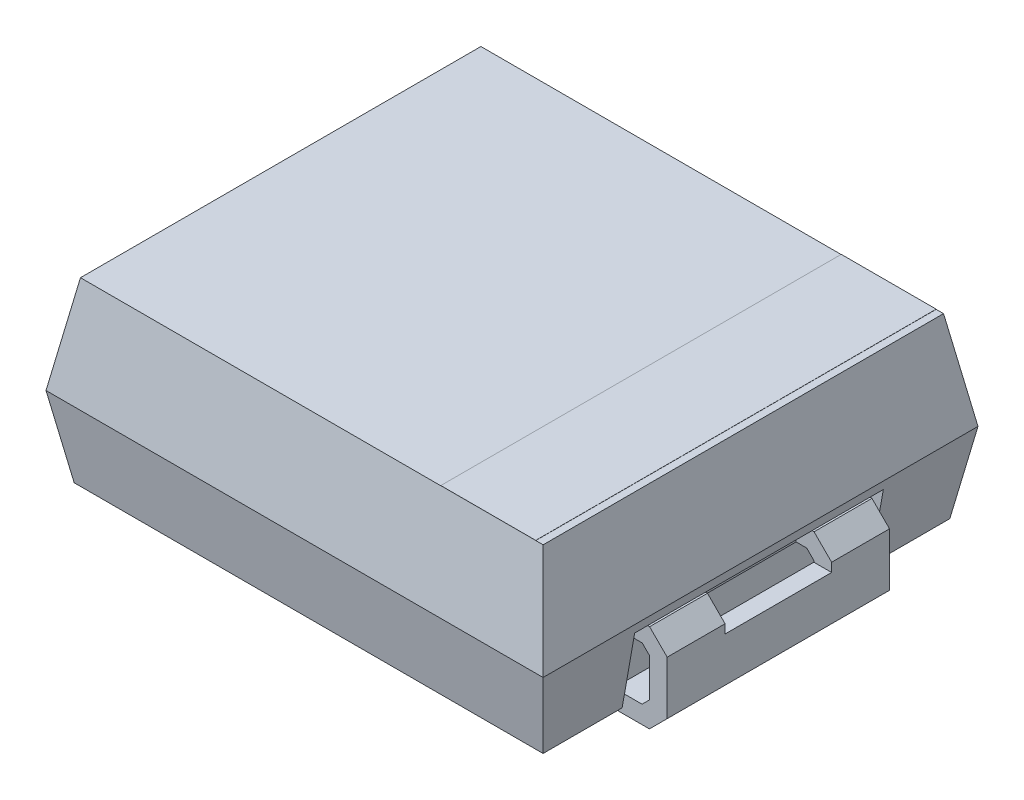
SolidWorks part; units mm, degrees
ref_plane "Front Plane" through (0, 0, 0) normal (0, 0, 1) x (1, 0, 0)
ref_plane "Top Plane" through (0, 0, 0) normal (0, 1, 0) x (1, 0, 0)
ref_plane "Right Plane" through (0, 0, 0) normal (1, 0, 0) x (0, 0, -1)
sketch "Sketch2" plane through (0, 0, 0) normal (1, 0, 0) x (0, 0, -1)
  line L1 (3.11, 2.794) -> (-3.11, 2.794)
  line L2 (3.11, 2.794) -> (3.11, 0)
  line L3 (3.11, 0) -> (-3.11, 0)
  line L4 (-3.11, 2.794) -> (-3.11, 0)
  dimension "D1" = 2.794
  dimension "D2" = 6.22
extrude "Base-Extrude" add sketch "Sketch2" along normal blind 7.1095
chamfer "Chamfer1" distance 1.397 angle 10 4 edges at (7.1095, 0, 0) (0, 0, 0) (3.5547, 0, -3.11) (3.5547, 0, 3.11)
sketch "Sketch3" plane through (0, 0, 0) normal (-1, 0, 0) x (0, 0, 1)
  line L0 (2.8636, 0) -> (-2.8636, 0) construction
  line L1 (-1.778, 1.27) -> (1.778, 1.27)
  line L2 (-1.778, 1.27) -> (-1.778, 0)
  line L3 (-1.778, 0) -> (1.778, 0)
  line L4 (1.778, 1.27) -> (1.778, 0)
  dimension "D1" = 1.27
  dimension "D2" = 1.778
  dimension "D3" = 3.556
extrude "Cut-Extrude1" cut sketch "Sketch3" against normal blind 0.508
sketch "Sketch4" plane through (7.1095, 0, 0) normal (1, 0, 0) x (0, 0, -1)
  line L0 (-1.778, 0) -> (1.778, 0)
  line L1 (2.8636, 0) -> (-2.8636, 0) construction
  line L2 (-1.778, 1.27) -> (1.778, 1.27)
  line L3 (1.778, 0) -> (1.778, 1.27)
  line L4 (-1.778, 0) -> (-1.778, 1.27)
  dimension "D1" = 3.556
  dimension "D2" = 1.778
  dimension "D3" = 1.27
extrude "Cut-Extrude2" cut sketch "Sketch4" against normal blind 0.508
sketch "Sketch5" plane through (0, 0, 0) normal (0, -1, 0) x (1, 0, 0)
  line L1 (5.207, -1.8001) -> (1.905, -1.8001)
  line L2 (5.207, -1.8001) -> (5.207, 1.8001)
  line L3 (5.207, 1.8001) -> (1.905, 1.8001)
  line L4 (1.905, -1.8001) -> (1.905, 1.8001)
  dimension "D1" = 3.6002
  dimension "D2" = 1.8001
  dimension "D3" = 1.905
  dimension "D4" = 3.302
extrude "Cut-Extrude3" cut sketch "Sketch5" against normal blind 0.254 flip side to cut
chamfer "Chamfer2" distance 1.397 angle 10 8 edges at (7.1095, 2.0955, 3.11) (0, 2.0955, -3.11) (7.1095, 2.0955, -3.11) (0, 2.0955, 3.11) (0, 2.794, 0) (7.1095, 2.794, 0) (3.5547, 2.794, 3.11) (3.5547, 2.794, -3.11)
sketch "Sketch6" plane through (0, 0, 0) normal (0, 0, 1) x (1, 0, 0)
  line L0 (0, 0) -> (1.2954, 0)
  line L1 (-0.254, 0.254) -> (-0.254, 1.016)
  line L2 (0, 0) -> (-0.254, 0.254)
  line L3 (-0.254, 1.016) -> (-0.0026, 1.2674)
  line L4 (-0.0026, 1.2674) -> (0.2955, 1.2674)
  dimension "D1" = 1.2954
  dimension "D2" = 135
  dimension "D3" = 0.254
  dimension "D4" = 0.762
  dimension "D5" = 135
  dimension "D6" = 0.3556
extrude "Boss-Extrude-Thin1" add sketch "Sketch6" along normal mid plane 3.1798 thin thin type one direction wall 0.254
sketch "Sketch7" plane through (-0.254, 0, 0) normal (-1, 0, 0) x (0, 0, 1)
  line L0 (1.778, 1.27) -> (-1.778, 1.27) construction
  line L1 (-0.762, 0.889) -> (0.762, 0.889)
  line L2 (-0.762, 0.889) -> (-0.762, 1.27)
  line L3 (-0.762, 1.27) -> (0.762, 1.27)
  line L4 (0.762, 0.889) -> (0.762, 1.27)
  dimension "D1" = 0.381
  dimension "D2" = 0.762
  dimension "D3" = 1.524
extrude "Cut-Extrude4" cut sketch "Sketch7" against normal blind 0.508
ref_plane "Plane6" through (3.555, 0, 0) normal (1, 0, 0) x (0, 0, -1)
mirror "Mirror1" about plane through (3.555, 0, 0) normal (1, 0, 0) of "Cut-Extrude4", "Boss-Extrude-Thin1"
sketch "Sketch8" plane through (0, 2.794, 0) normal (0, 1, 0) x (-1, 0, 0)
  line L0 (-6.8631, -2.8636) -> (-0.2463, -2.8636) construction
  line L1 (-5.4, -2.8636) -> (-6.7577, -2.8636)
  line L2 (-5.4, -2.8636) -> (-5.4, 2.8636)
  line L3 (-5.4, 2.8636) -> (-6.7577, 2.8636)
  line L4 (-6.7577, -2.8636) -> (-6.7577, 2.8636)
  line L5 (-0.2463, 2.8636) -> (-6.8631, 2.8636) construction
  dimension "D1" = 5.4
  dimension "D2" = 1.3576
extrude "Boss-Extrude2" add sketch "Sketch8" along normal blind 0.0025
sketch "Component_Outline" plane through (0, 0, 0) normal (0, 1, 0) x (1, 0, 0)
  line L0 (7.1095, -3.11) -> (7.11, -1.5899)
  line L1 (7.11, -1.5899) -> (7.364, -1.5899)
  line L2 (7.364, -1.5899) -> (7.364, 1.5899)
  line L3 (7.364, 1.5899) -> (7.11, 1.5899)
  line L4 (7.11, 1.5899) -> (7.1095, 3.11)
  line L5 (7.1095, 3.11) -> (0, 3.11)
  line L6 (0, 3.11) -> (0, 1.5899)
  line L7 (0, 1.5899) -> (-0.254, 1.5899)
  line L8 (-0.254, 1.5899) -> (-0.254, -1.5899)
  line L9 (-0.254, -1.5899) -> (0, -1.5899)
  line L10 (0, -1.5899) -> (0, -3.11)
  line L11 (0, -3.11) -> (7.1095, -3.11)
